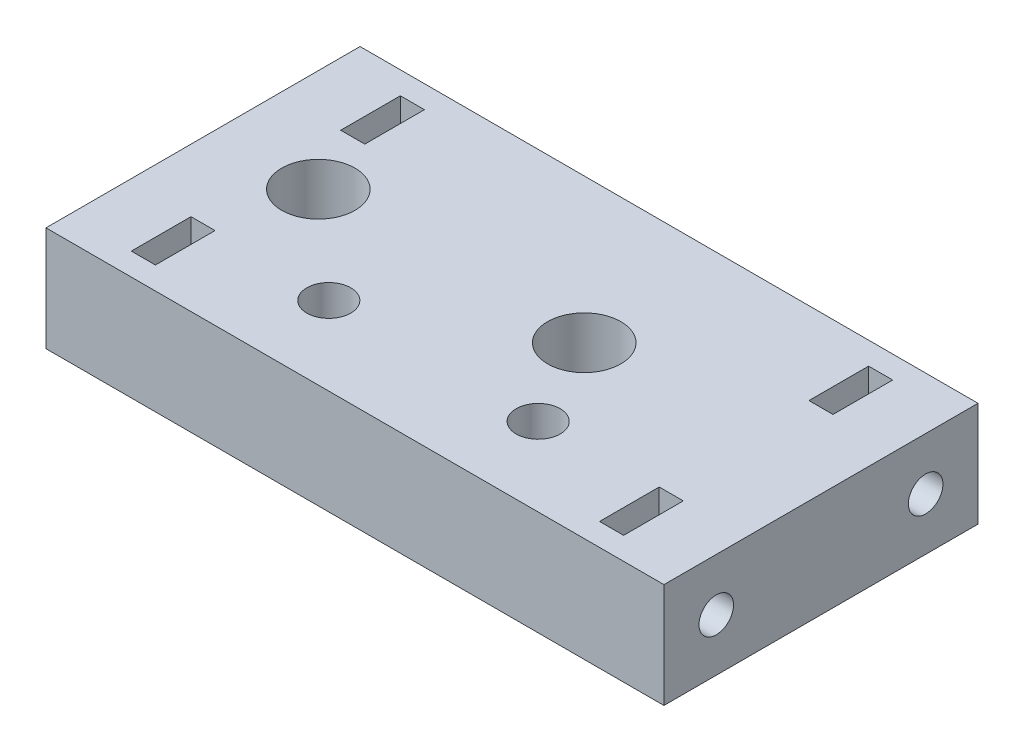
SolidWorks part; units mm, degrees
ref_plane "Front Plane" through (0, 0, 0) normal (0, 0, 1) x (1, 0, 0)
ref_plane "Top Plane" through (0, 0, 0) normal (0, 1, 0) x (1, 0, 0)
ref_plane "Right Plane" through (0, 0, 0) normal (1, 0, 0) x (0, 0, -1)
sketch "Sketch1" plane through (0, 0, 0) normal (0, 1, 0) x (1, 0, 0)
  line L1 (-29.5136, -15) -> (29.5136, -15)
  line L2 (-29.5136, -15) -> (-29.5136, 15)
  line L3 (-29.5136, 15) -> (29.5136, 15)
  line L4 (29.5136, -15) -> (29.5136, 15)
  line L5 (-29.5136, -15) -> (29.5136, 15) construction
  line L6 (-29.5136, 15) -> (29.5136, -15) construction
  point P0 (0, 0)
  dimension "D1" = 59.0272
  dimension "D2" = 30
extrude "Boss-Extrude1" add sketch "Sketch1" along normal blind 10
sketch "Sketch2" plane through (0, 10, 0) normal (0, 1, 0) x (1, 0, 0)
  line L0 (-10, -7.5) -> (10, -7.5) construction
  line L3 (0, 15) -> (0, -15) construction
  line L4 (29.5136, 15) -> (-29.5136, 15) construction
  line L5 (-29.5136, -15) -> (29.5136, -15) construction
  circle A0 centre (-10, -7.5) radius 2.1
  circle A1 centre (10, -7.5) radius 2.1
  point P3 (0, -7.5)
  dimension "D1" = 4.2
  dimension "D2" = 20
  dimension "D3" = 7.5
extrude "Cut-Extrude1" cut sketch "Sketch2" against normal through all
sketch "Sketch3" plane through (29.5136, 0, 0) normal (1, 0, 0) x (0, 0, -1)
  line L0 (0, 10) -> (0, 0) construction
  line L1 (-15, 10) -> (15, 10) construction
  line L2 (-15, 0) -> (15, 0) construction
  line L3 (-10, 5) -> (10, 5) construction
  circle A0 centre (-10, 5) radius 1.65
  circle A1 centre (10, 5) radius 1.65
  point P9 (0, 5)
  dimension "D2" = 3.3
  dimension "D1" = 20
extrude "Cut-Extrude2" cut sketch "Sketch3" against normal blind 12
sketch "Sketch4" plane through (-29.5136, 0, 0) normal (-1, 0, 0) x (0, 0, 1)
  line L0 (0, 10) -> (0, 0) construction
  line L3 (-10, 5) -> (10, 5) construction
  line L4 (-15, 10) -> (15, 10) construction
  circle A0 centre (-10, 5) radius 1.65
  circle A1 centre (10, 5) radius 1.65
  point P9 (0, 5)
  dimension "D2" = 3.3
  dimension "D1" = 20
extrude "Cut-Extrude3" cut sketch "Sketch4" against normal blind 12
ref_plane "Plane1" through (23.5136, 0, 0) normal (1, 0, 0) x (0, 0, -1)
ref_plane "Plane2" through (-23.5136, 0, 0) normal (-1, 0, 0) x (0, 0, 1)
sketch "Sketch5" plane through (23.5136, 0, 0) normal (1, 0, 0) x (0, 0, -1)
  line L0 (-12.85, 6.6454) -> (-12.85, 10)
  line L1 (-7.15, 6.6454) -> (-10, 8.2909) construction
  line L2 (-10, 8.2909) -> (-12.85, 6.6454) construction
  line L3 (-12.85, 6.6454) -> (-12.85, 3.3546)
  line L4 (-12.85, 3.3546) -> (-10, 1.7091)
  line L5 (-10, 1.7091) -> (-7.15, 3.3546)
  line L6 (-7.15, 3.3546) -> (-7.15, 6.6454)
  line L7 (10, 8.2909) -> (7.15, 6.6454) construction
  line L8 (7.15, 6.6454) -> (7.15, 3.3546)
  line L9 (7.15, 3.3546) -> (10, 1.7091)
  line L10 (10, 1.7091) -> (12.85, 3.3546)
  line L11 (12.85, 3.3546) -> (12.85, 6.6454)
  line L12 (12.85, 6.6454) -> (10, 8.2909) construction
  line L13 (-15, 10) -> (15, 10) construction
  line L14 (-12.85, 10) -> (-7.15, 10)
  line L15 (-7.15, 10) -> (-7.15, 6.6454)
  line L16 (7.15, 6.6454) -> (7.15, 10)
  line L17 (7.15, 10) -> (12.85, 10)
  line L18 (12.85, 10) -> (12.85, 6.6454)
  circle A0 centre (-10, 5) radius 2.85 construction
  circle A1 centre (10, 5) radius 2.85 construction
  dimension "D1" = 5.7
extrude "Cut-Extrude4" cut sketch "Sketch5" against normal blind 2.3
sketch "Sketch6" plane through (-23.5136, 0, 0) normal (-1, 0, 0) x (0, 0, 1)
  line L0 (-12.85, 6.6454) -> (-12.85, 10)
  line L1 (-7.15, 6.6454) -> (-10, 8.2909) construction
  line L2 (-10, 8.2909) -> (-12.85, 6.6454) construction
  line L3 (-12.85, 6.6454) -> (-12.85, 3.3546)
  line L4 (-12.85, 3.3546) -> (-10, 1.7091)
  line L5 (-10, 1.7091) -> (-7.15, 3.3546)
  line L6 (-7.15, 3.3546) -> (-7.15, 6.6454)
  line L7 (10, 8.2909) -> (7.15, 6.6454) construction
  line L8 (7.15, 6.6454) -> (7.15, 3.3546)
  line L9 (7.15, 3.3546) -> (10, 1.7091)
  line L10 (10, 1.7091) -> (12.85, 3.3546)
  line L11 (12.85, 3.3546) -> (12.85, 6.6454)
  line L12 (12.85, 6.6454) -> (10, 8.2909) construction
  line L14 (-12.85, 10) -> (-7.15, 10)
  line L15 (-7.15, 10) -> (-7.15, 6.6454)
  line L16 (7.15, 6.6454) -> (7.15, 10)
  line L17 (7.15, 10) -> (12.85, 10)
  line L18 (12.85, 10) -> (12.85, 6.6454)
  line L19 (-15, 10) -> (15, 10) construction
  circle A0 centre (-10, 5) radius 2.85 construction
  circle A1 centre (10, 5) radius 2.85 construction
  circle A2 centre (-10, 5) radius 1.65 construction
  circle A3 centre (-10, 5) radius 1.65 construction
  circle A5 centre (10, 5) radius 1.65 construction
  circle A6 centre (10, 5) radius 1.65 construction
  dimension "D1" = 5.7
extrude "Cut-Extrude5" cut sketch "Sketch6" against normal blind 2.3
sketch "Sketch7" plane through (0, 10, 0) normal (0, 1, 0) x (1, 0, 0)
  line L1 (-29.5136, -15) -> (29.5136, -15) construction
  line L2 (5.7, 1.2) -> (-19.7, 1.2) construction
  line L3 (-29.5136, 15) -> (-29.5136, -15) construction
  circle A0 centre (5.7, 1.2) radius 3.5
  circle A1 centre (-19.7, 1.2) radius 3.5
  dimension "D3" = 7
  dimension "D1" = 9.8136
  dimension "D2" = 16.2
  dimension "D4" = 25.4
extrude "Cut-Extrude6" cut sketch "Sketch7" against normal through all
